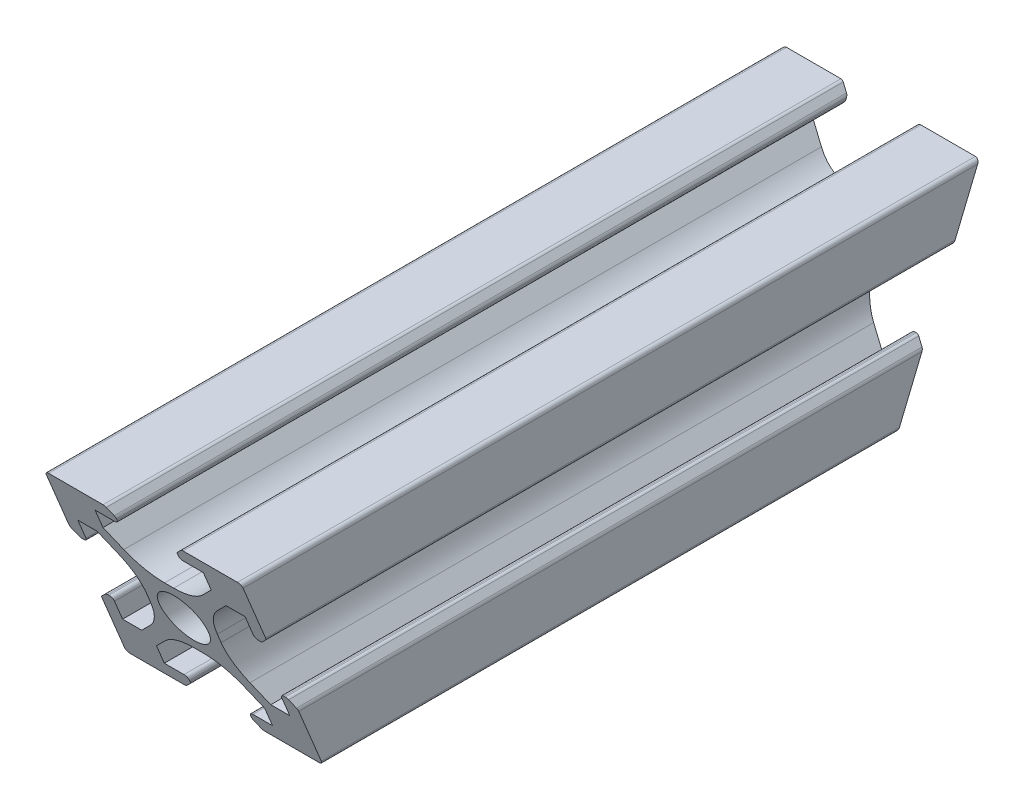
SolidWorks part; units mm, degrees
material "6063-T83"
ref_plane "Plano frontal" through (0, 0, 0) normal (0, 0, 1) x (1, 0, 0)
ref_plane "Plano superior" through (0, 0, 0) normal (0, 1, 0) x (1, 0, 0)
ref_plane "Plano direito" through (0, 0, 0) normal (1, 0, 0) x (0, 0, -1)
sketch "Esboço1" plane through (0, 0, 0) normal (0, 0, 1) x (1, 0, 0)
  line L0 (-9.0343, 3.1) -> (-8.9, 3.1)
  line L3 (-10, 10) -> (-4.0657, 10)
  line L5 (-10, -10) -> (10, 10) construction
  line L6 (-10, 10) -> (10, -10) construction
  line L7 (-8.5, 3.5) -> (-8.5, 5.5)
  line L8 (-10, 0) -> (10, 0) construction
  line L9 (0, 10) -> (0, -10) construction
  line L12 (-8.5, 5.5) -> (-6.5607, 5.5)
  line L15 (-6.5607, 5.5) -> (-5.0645, 4.0038)
  line L16 (-3.6, 0.4683) -> (-3.6, 0)
  line L17 (-0.4683, 3.6) -> (0, 3.6)
  line L18 (-5.5, 6.5607) -> (-4.0038, 5.0645)
  line L21 (-5.5, 8.5) -> (-5.5, 6.5607)
  line L24 (-3.5, 8.5) -> (-5.5, 8.5)
  line L25 (-3.1, 9.0343) -> (-3.1, 8.9)
  line L44 (-10, 4.0657) -> (-10, 10)
  line L45 (-9.8828, 3.7828) -> (-9.3172, 3.2172)
  line L46 (-3.7828, 9.8828) -> (-3.2172, 9.3172)
  line L47 (-3.6, 0) -> (-2.5, 0)
  line L48 (0, 3.6) -> (0, 2.5)
  arc A0 (-3.5, 8.5) -> (-3.1, 8.9) centre (-3.5, 8.9) ccw
  arc A1 (-3.7828, 9.8828) -> (-4.0657, 10) centre (-4.0657, 9.6) ccw
  arc A2 (-10, 4.0657) -> (-9.8828, 3.7828) centre (-9.6, 4.0657) ccw
  arc A3 (-8.5, 3.5) -> (-8.9, 3.1) centre (-8.9, 3.5) cw
  arc A4 (-3.2172, 9.3172) -> (-3.1, 9.0343) centre (-3.5, 9.0343) cw
  arc A5 (-9.3172, 3.2172) -> (-9.0343, 3.1) centre (-9.0343, 3.5) ccw
  arc A6 (-3.6, 0.4683) -> (-5.0645, 4.0038) centre (-8.6, 0.4683) ccw
  arc A7 (-4.0038, 5.0645) -> (-0.4683, 3.6) centre (-0.4683, 8.6) ccw
  circle A8 centre (0, 0) radius 2.5
  point P6 (-10, 3.1)
  point P28 (-3.1, 8.5)
  point P31 (-3.1, 10)
  point P33 (-3.9, 10)
  point P36 (-10, 3.9)
  point P39 (-8.5, 3.1)
  point P42 (-3.1, 9.2)
  point P45 (-9.2, 3.1)
  point P48 (-3.6, 2.5393)
  point P51 (-2.5393, 3.6)
  dimension "D5" = 10
  dimension "D9" = 0.4
  dimension "D10" = 0.4
  dimension "D11" = 5
  dimension "D12" = 5
  dimension "D13" = 5
  dimension "D1" = 6.9
  dimension "D2" = 1.5
  dimension "D3" = 3.6
  dimension "D4" = 1.5
  dimension "D6" = 2.4
  dimension "D7" = 3.6
  dimension "D8" = 45
extrude "Ressalto-extrusão1" add sketch "Esboço1" along normal blind 75 contours A4 A3 L3 A0 L17 L18 L21 L24 L25 L0 L7 L12 L15 L16 region at (-5.9987, 5.9987, 0)
sketch "Esboço3" plane through (0, 0, 0) normal (1, 0, 0) x (0, 0, -1)
  line L0 (0, 0) -> (-75, 0) construction
  line L1 (-75, 2.5) -> (-75, 0) construction
pattern_circular "PadrãoCircular1" count 4 every 90 about axis through (0, 0, 0) along (0, 0, 1) of "Ressalto-extrusão1"
fillet "Filete1" radius 0.4 4 edges at (-10, -10, 37.5) (-10, 10, 37.5) (10, -10, 37.5) (10, 10, 37.5)
ref_plane "Plane1" through (0, 0, 37.5) normal (0, 0, 1) x (1, 0, 0)
sketch "Sketch1" plane through (-10, 0, 0) normal (-1, 0, 0) x (0, 0, 1)
  line L0 (0, 10) -> (0, -10)
  line L1 (0, 0) -> (75, 0) construction
  line L2 (0, 10) -> (8.2843, -10)
  line L3 (0, -10) -> (8.2843, -10)
  line L4 (37.5, 9.6) -> (37.5, -9.6) construction
  line L5 (75, 9.6) -> (0, 9.6) construction
  line L6 (0, -9.6) -> (75, -9.6) construction
  line L7 (75, 9.6) -> (75, -9.6)
  line L8 (75, -10) -> (66.7157, -10)
  line L9 (75, 10) -> (66.7157, -10)
  line L10 (75, 10) -> (75, -10)
  line M5 (75, 4.0657) -> (75, 9.6)
  line M6 (75, 9.6) -> (0, 9.6)
  line M7 (0, 9.6) -> (0, 4.0657)
  line M8 (0, 4.0657) -> (75, 4.0657)
  dimension "D1" = 10
  dimension "D2" = 22.5
extrude "Cut-Extrude1" cut sketch "Sketch1" against normal through all contours L0 L3 L2 M8 | L2 M6 M7 M8 | L9 M6 M8 M5 | L10 L7 L9 L8 M8 | L10 L9 M6 | L2 L0 M6 region at (-10, 9.7333, 0.0552) region at (-10, 6.027, 0.8228) region at (-10, -4.2386, 2.9489) region at (-10, 6.027, 74.1772) region at (-10, 9.7333, 74.9448) region at (-10, -4.2386, 72.0511)
